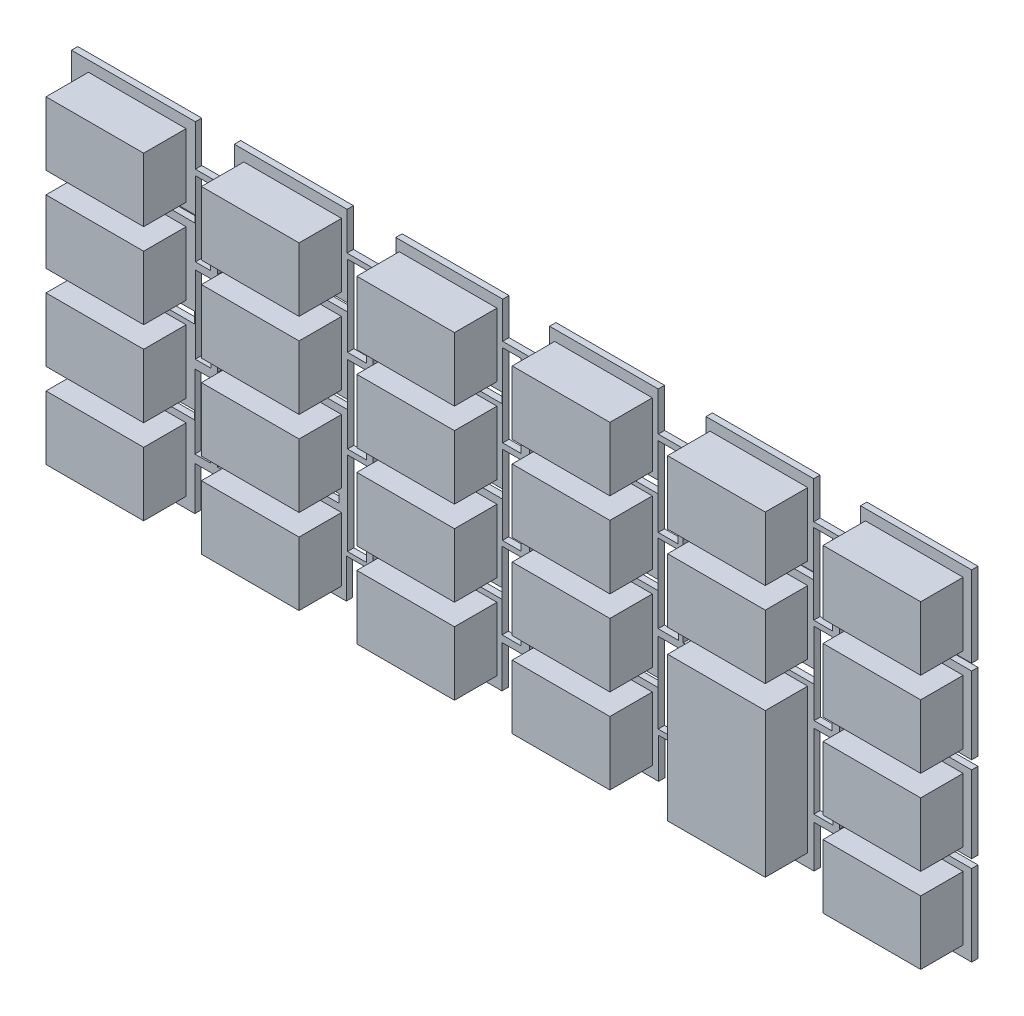
SolidWorks part; units mm, degrees
ref_plane "Front Plane" through (0, 0, 0) normal (0, 0, 1) x (1, 0, 0)
ref_plane "Top Plane" through (0, 0, 0) normal (0, 1, 0) x (1, 0, 0)
ref_plane "Right Plane" through (0, 0, 0) normal (1, 0, 0) x (0, 0, -1)
sketch "Sketch1" plane through (0, 0, 0) normal (0, 0, 1) x (1, 0, 0)
  line L1 (64.5, -22) -> (-64.5, -22)
  line L2 (64.5, -22) -> (64.5, 22)
  line L3 (64.5, 22) -> (-64.5, 22)
  line L4 (-64.5, -22) -> (-64.5, 22)
  line L5 (64.5, -22) -> (-64.5, 22) construction
  line L6 (64.5, 22) -> (-64.5, -22) construction
  point P0 (0, 0)
  dimension "D1" = 129
  dimension "D2" = 44
extrude "main_body" add sketch "Sketch1" along normal blind 0.75
sketch "Sketch2" plane through (0, 0, 0.75) normal (0, 0, 1) x (1, 0, 0)
  line L0 (46.25, 22) -> (46.25, -22) construction
  line L1 (64.5, 22) -> (-64.5, 22) construction
  line L2 (-64.5, -22) -> (64.5, -22) construction
  line L3 (64.5, -22) -> (64.5, 22) construction
  line L4 (36.95, -5) -> (36.95, -15) construction
  line L5 (27.95, -22) -> (27.95, 22) construction
  line L6 (-64.5, 22) -> (-64.5, -22) construction
  line L7 (-39.5, 11.25) -> (-51, 11.25)
  line L8 (9.65, 22) -> (9.65, -22) construction
  line L9 (-39.5, 1.25) -> (-51, 1.25)
  line L10 (64.5, 5) -> (-64.5, 5) construction
  line L11 (-8.65, -22) -> (-8.65, 22) construction
  line L12 (-39.5, 1.25) -> (-39.5, 8.75)
  line L13 (-39.5, 8.75) -> (-51, 8.75)
  line L14 (-26.95, 22) -> (-26.95, -22) construction
  line L15 (-64.5, 15) -> (64.5, 15) construction
  line L16 (-51, 1.25) -> (-51, 8.75)
  line L17 (-45.25, -22) -> (-45.25, 22) construction
  line L18 (-39.5, 1.25) -> (-51, 8.75) construction
  line L19 (64.5, -5) -> (-64.5, -5) construction
  line L20 (-39.5, 8.75) -> (-51, 1.25) construction
  line L21 (-21.2, 1.25) -> (-32.7, 1.25)
  line L22 (-64.5, -15) -> (64.5, -15) construction
  line L23 (-21.2, 1.25) -> (-21.2, 8.75)
  line L24 (-21.2, 8.75) -> (-32.7, 8.75)
  line L25 (-32.7, 1.25) -> (-32.7, 8.75)
  line L26 (-21.2, 1.25) -> (-32.7, 8.75) construction
  line L27 (-21.2, 8.75) -> (-32.7, 1.25) construction
  line L28 (-2.9, 1.25) -> (-14.4, 1.25)
  line L29 (-2.9, 1.25) -> (-2.9, 8.75)
  line L30 (-2.9, 8.75) -> (-14.4, 8.75)
  line L31 (-14.4, 1.25) -> (-14.4, 8.75)
  line L32 (-2.9, 1.25) -> (-14.4, 8.75) construction
  line L33 (-2.9, 8.75) -> (-14.4, 1.25) construction
  line L34 (15.4, 1.25) -> (3.9, 1.25)
  line L35 (15.4, 1.25) -> (15.4, 8.75)
  line L36 (15.4, 8.75) -> (3.9, 8.75)
  line L37 (3.9, 1.25) -> (3.9, 8.75)
  line L38 (15.4, 1.25) -> (3.9, 8.75) construction
  line L39 (15.4, 8.75) -> (3.9, 1.25) construction
  line L40 (33.7, 1.25) -> (22.2, 1.25)
  line L41 (33.7, 1.25) -> (33.7, 8.75)
  line L42 (33.7, 8.75) -> (22.2, 8.75)
  line L43 (22.2, 1.25) -> (22.2, 8.75)
  line L44 (33.7, 1.25) -> (22.2, 8.75) construction
  line L45 (33.7, 8.75) -> (22.2, 1.25) construction
  line L46 (52, -8.75) -> (40.5, -8.75)
  line L47 (52, -8.75) -> (52, -1.25)
  line L48 (52, -1.25) -> (40.5, -1.25)
  line L49 (40.5, -8.75) -> (40.5, -1.25)
  line L50 (52, -8.75) -> (40.5, -1.25) construction
  line L51 (52, -1.25) -> (40.5, -8.75) construction
  line L52 (52, -18.75) -> (40.5, -18.75)
  line L53 (52, -18.75) -> (52, -11.25)
  line L54 (52, -11.25) -> (40.5, -11.25)
  line L55 (40.5, -18.75) -> (40.5, -11.25)
  line L56 (52, -18.75) -> (40.5, -11.25) construction
  line L57 (52, -11.25) -> (40.5, -18.75) construction
  line L58 (52, 11.25) -> (40.5, 11.25)
  line L59 (52, 11.25) -> (52, 18.75)
  line L60 (52, 18.75) -> (40.5, 18.75)
  line L61 (40.5, 11.25) -> (40.5, 18.75)
  line L62 (52, 11.25) -> (40.5, 18.75) construction
  line L63 (52, 18.75) -> (40.5, 11.25) construction
  line L64 (-39.5, 11.25) -> (-39.5, 18.75)
  line L65 (-39.5, 18.75) -> (-51, 18.75)
  line L66 (-51, 11.25) -> (-51, 18.75)
  line L67 (-39.5, 11.25) -> (-51, 18.75) construction
  line L68 (-39.5, 18.75) -> (-51, 11.25) construction
  line L69 (-39.5, -8.75) -> (-51, -8.75)
  line L70 (-39.5, -8.75) -> (-39.5, -1.25)
  line L71 (-39.5, -1.25) -> (-51, -1.25)
  line L72 (-51, -8.75) -> (-51, -1.25)
  line L73 (-39.5, -8.75) -> (-51, -1.25) construction
  line L74 (-39.5, -1.25) -> (-51, -8.75) construction
  line L75 (-39.5, -18.75) -> (-51, -18.75)
  line L76 (-39.5, -18.75) -> (-39.5, -11.25)
  line L77 (-39.5, -11.25) -> (-51, -11.25)
  line L78 (-51, -18.75) -> (-51, -11.25)
  line L79 (-39.5, -18.75) -> (-51, -11.25) construction
  line L80 (-39.5, -11.25) -> (-51, -18.75) construction
  line L81 (-21.2, 11.25) -> (-32.7, 11.25)
  line L82 (-21.2, 11.25) -> (-21.2, 18.75)
  line L83 (-21.2, 18.75) -> (-32.7, 18.75)
  line L84 (-32.7, 11.25) -> (-32.7, 18.75)
  line L85 (-21.2, 11.25) -> (-32.7, 18.75) construction
  line L86 (-21.2, 18.75) -> (-32.7, 11.25) construction
  line L87 (-21.2, -8.75) -> (-32.7, -8.75)
  line L88 (-21.2, -8.75) -> (-21.2, -1.25)
  line L89 (-21.2, -1.25) -> (-32.7, -1.25)
  line L90 (-32.7, -8.75) -> (-32.7, -1.25)
  line L91 (-21.2, -8.75) -> (-32.7, -1.25) construction
  line L92 (-21.2, -1.25) -> (-32.7, -8.75) construction
  line L93 (-21.2, -18.75) -> (-32.7, -18.75)
  line L94 (-21.2, -18.75) -> (-21.2, -11.25)
  line L95 (-21.2, -11.25) -> (-32.7, -11.25)
  line L96 (-32.7, -18.75) -> (-32.7, -11.25)
  line L97 (-21.2, -18.75) -> (-32.7, -11.25) construction
  line L98 (-21.2, -11.25) -> (-32.7, -18.75) construction
  line L99 (-2.9, -8.75) -> (-14.4, -8.75)
  line L100 (-2.9, -8.75) -> (-2.9, -1.25)
  line L101 (-2.9, -1.25) -> (-14.4, -1.25)
  line L102 (-14.4, -8.75) -> (-14.4, -1.25)
  line L103 (-2.9, -8.75) -> (-14.4, -1.25) construction
  line L104 (-2.9, -1.25) -> (-14.4, -8.75) construction
  line L105 (-2.9, -18.75) -> (-14.4, -18.75)
  line L106 (-2.9, -18.75) -> (-2.9, -11.25)
  line L107 (-2.9, -11.25) -> (-14.4, -11.25)
  line L108 (-14.4, -18.75) -> (-14.4, -11.25)
  line L109 (-2.9, -18.75) -> (-14.4, -11.25) construction
  line L110 (-2.9, -11.25) -> (-14.4, -18.75) construction
  line L111 (-2.9, 11.25) -> (-14.4, 11.25)
  line L112 (-2.9, 11.25) -> (-2.9, 18.75)
  line L113 (-2.9, 18.75) -> (-14.4, 18.75)
  line L114 (-14.4, 11.25) -> (-14.4, 18.75)
  line L115 (-2.9, 11.25) -> (-14.4, 18.75) construction
  line L116 (-2.9, 18.75) -> (-14.4, 11.25) construction
  line L117 (15.4, 11.25) -> (3.9, 11.25)
  line L118 (15.4, 11.25) -> (15.4, 18.75)
  line L119 (15.4, 18.75) -> (3.9, 18.75)
  line L120 (3.9, 11.25) -> (3.9, 18.75)
  line L121 (15.4, 11.25) -> (3.9, 18.75) construction
  line L122 (15.4, 18.75) -> (3.9, 11.25) construction
  line L123 (15.4, -8.75) -> (3.9, -8.75)
  line L124 (15.4, -8.75) -> (15.4, -1.25)
  line L125 (15.4, -1.25) -> (3.9, -1.25)
  line L126 (3.9, -8.75) -> (3.9, -1.25)
  line L127 (15.4, -8.75) -> (3.9, -1.25) construction
  line L128 (15.4, -1.25) -> (3.9, -8.75) construction
  line L129 (15.4, -18.75) -> (3.9, -18.75)
  line L130 (15.4, -18.75) -> (15.4, -11.25)
  line L131 (15.4, -11.25) -> (3.9, -11.25)
  line L132 (3.9, -18.75) -> (3.9, -11.25)
  line L133 (15.4, -18.75) -> (3.9, -11.25) construction
  line L134 (15.4, -11.25) -> (3.9, -18.75) construction
  line L135 (33.7, 11.25) -> (22.2, 11.25)
  line L136 (33.7, 11.25) -> (33.7, 18.75)
  line L137 (33.7, 18.75) -> (22.2, 18.75)
  line L138 (22.2, 11.25) -> (22.2, 18.75)
  line L139 (33.7, 11.25) -> (22.2, 18.75) construction
  line L140 (33.7, 18.75) -> (22.2, 11.25) construction
  line L141 (52, 1.25) -> (40.5, 1.25)
  line L142 (52, 1.25) -> (52, 8.75)
  line L143 (52, 8.75) -> (40.5, 8.75)
  line L144 (40.5, 1.25) -> (40.5, 8.75)
  line L145 (52, 1.25) -> (40.5, 8.75) construction
  line L146 (52, 8.75) -> (40.5, 1.25) construction
  line L147 (36.95, -10) -> (27.95, -10) construction
  line L149 (33.7, -18.5) -> (22.2, -18.5)
  line L150 (33.7, -18.5) -> (33.7, -1.5)
  line L151 (33.7, -1.5) -> (22.2, -1.5)
  line L152 (22.2, -18.5) -> (22.2, -1.5)
  line L153 (33.7, -18.5) -> (22.2, -1.5) construction
  line L154 (33.7, -1.5) -> (22.2, -18.5) construction
  point P13 (-45.25, 15)
  point P23 (-45.25, 5)
  point P35 (-26.95, 5)
  point P40 (-8.65, 5)
  point P45 (9.65, 5)
  point P50 (27.95, 5)
  point P55 (46.25, -5)
  point P60 (46.25, -15)
  point P65 (46.25, 15)
  point P70 (-45.25, -5)
  point P75 (-45.25, -15)
  point P80 (-26.95, 15)
  point P88 (-26.95, -5)
  point P93 (-26.95, -15)
  point P98 (-8.65, -15)
  point P100 (-8.65, -5)
  point P108 (-8.65, 15)
  point P113 (9.65, 15)
  point P118 (9.65, -5)
  point P123 (9.65, -15)
  point P128 (27.95, 15)
  point P133 (46.25, 5)
  point P142 (27.95, -10)
  dimension "D1" = 18.25
  dimension "D3" = 18.3
  dimension "D4" = 18.3
  dimension "D5" = 18.3
  dimension "D6" = 18.3
  dimension "D7" = 10
  dimension "D8" = 7
  dimension "D9" = 10
  dimension "D10" = 10
  dimension "D11" = 11.5
  dimension "D12" = 11.5
  dimension "D13" = 11.5
  dimension "D14" = 11.5
  dimension "D15" = 7.5
  dimension "D16" = 7.5
  dimension "D17" = 7.5
  dimension "D18" = 7.5
  dimension "D19" = 7.5
  dimension "D20" = 7.5
  dimension "D21" = 11.5
  dimension "D22" = 11.5
  dimension "D23" = 7.5
  dimension "D24" = 11.5
  dimension "D25" = 11.5
  dimension "D26" = 7.5
  dimension "D27" = 7
  dimension "D28" = 18.3
  dimension "D29" = 19.25
  dimension "D30" = 9
  dimension "D31" = 5
  dimension "D32" = 5
  dimension "D33" = 11.5
  dimension "D34" = 7.5
  dimension "D35" = 11.5
  dimension "D36" = 7.5
  dimension "D37" = 11.5
  dimension "D38" = 7.5
  dimension "D39" = 11.5
  dimension "D40" = 7.5
  dimension "D41" = 11.5
  dimension "D42" = 7.5
  dimension "D43" = 11.5
  dimension "D44" = 7.5
  dimension "D45" = 11.5
  dimension "D46" = 17
  dimension "D47" = 11.5
  dimension "D48" = 7.5
  dimension "D49" = 11.5
  dimension "D50" = 7.5
  dimension "D51" = 11.5
  dimension "D52" = 11.5
  dimension "D53" = 11.5
  dimension "D54" = 11.5
  dimension "D55" = 11.5
  dimension "D56" = 11.5
  dimension "D57" = 7.5
  dimension "D58" = 7.5
  dimension "D59" = 7.5
  dimension "D60" = 7.5
  dimension "D61" = 7.5
  dimension "D62" = 7.5
extrude "button_bumps" add sketch "Sketch2" along normal blind 5
fillet "button_corners" [suppressed] radius 1
fillet "button_top" [suppressed] radius 1
sketch "Sketch3" [suppressed] plane through (0, 0, 5.5) normal (0, 0, 1) x (1, 0, 0)
  line L0 (-50.5, 22) -> (-50.5, -22) construction
  line L1 (61.5, 22) -> (-61.5, 22) construction
  line L2 (-61.5, -22) -> (61.5, -22) construction
  line L3 (-32.2, 22) -> (-32.2, -22) construction
  line L4 (64.5, -19) -> (64.5, 19) construction
  line L5 (-52.25, 14.5) -> (-38.25, 14.5) construction
  line L6 (-52.25, 18) -> (-52.25, 12) construction
  line L7 (-13.9, 22) -> (-13.9, -22) construction
  line L8 (-38.25, 12) -> (-38.25, 18) construction
  line L9 (2.65, -12) -> (2.65, -18) construction
  line L10 (20.95, -2.5) -> (20.95, -17.5) construction
  line L11 (39.25, -12) -> (39.25, -18) construction
  line L12 (-15.65, -12) -> (-15.65, -18) construction
  line L13 (4.4, -22) -> (4.4, 22) construction
  line L14 (-33.95, -12) -> (-33.95, -18) construction
  line L15 (-52.25, -12) -> (-52.25, -18) construction
  line L16 (22.7, 22) -> (22.7, -22) construction
  line L17 (-64.5, 13.5) -> (64.5, 13.5) construction
  line L18 (-64.5, 19) -> (-64.5, -19) construction
  line L19 (41, -22) -> (41, 22) construction
  line L20 (-64.5, 3.5) -> (64.5, 3.5) construction
  line L21 (-52.25, 4.5) -> (-38.25, 4.5) construction
  line L22 (-52.25, 8) -> (-52.25, 2) construction
  line L23 (-64.5, -6.5) -> (64.5, -6.5) construction
  line L24 (-38.25, 2) -> (-38.25, 8) construction
  line L25 (-52.25, -15.5) -> (-38.25, -15.5) construction
  line L26 (64.5, -16.5) -> (-64.5, -16.5) construction
  line L27 (-52.25, -12) -> (-52.25, -18) construction
  line L28 (-38.25, -8) -> (-38.25, -2) construction
  line L29 (-38.25, -5.5) -> (-52.25, -5.5) construction
  line L30 (-52.25, -2) -> (-52.25, -8) construction
  line L31 (-38.25, -18) -> (-38.25, -12) construction
  line L32 (-33.95, 12.5) -> (34.95, 12.5) construction
  line L33 (-33.95, 18) -> (-33.95, 12) construction
  line L34 (34.95, 12) -> (34.95, 18) construction
  line L35 (-33.95, 2.5) -> (34.95, 2.5) construction
  line L36 (-21.35, 19) -> (-21.35, -19) construction
  line L37 (-20.95, 19) -> (-32.95, 19) construction
  line L38 (-33.95, 8) -> (-33.95, 2) construction
  line L39 (34.95, 2) -> (34.95, 8) construction
  line L40 (-32.95, -19) -> (-20.95, -19) construction
  line L41 (-33.95, -7.5) -> (34.95, -7.5) construction
  line L42 (-19.95, -18) -> (-19.95, -12) construction
  line L43 (-33.95, -2) -> (-33.95, -8) construction
  line L44 (34.95, -17.5) -> (34.95, -2.5) construction
  line L45 (-3.05, 19) -> (-3.05, -19) construction
  line L46 (-33.95, -17.5) -> (34.95, -17.5) construction
  line L47 (-2.65, 19) -> (-14.65, 19) construction
  line L48 (-14.65, -19) -> (-2.65, -19) construction
  line L49 (-33.95, -12) -> (-33.95, -18) construction
  line L50 (-33.95, 15.3) -> (34.95, 15.3) construction
  line L51 (-33.95, 5.3) -> (34.95, 5.3) construction
  line L52 (-33.95, -4.7) -> (34.95, -4.7) construction
  line L53 (-33.95, -14.7) -> (34.95, -14.7) construction
  line L54 (-1.65, -18) -> (-1.65, -12) construction
  line L55 (-4.6, -14.55) -> (-3.2, -14.55)
  line L56 (15.25, 19) -> (15.25, -19) construction
  line L57 (-3.05, -14.7) -> (-4.75, -14.7)
  line L58 (15.65, 19) -> (3.65, 19) construction
  line L59 (-3.05, -14.7) -> (-3.05, -14.55)
  line L60 (3.65, -19) -> (15.65, -19) construction
  line L62 (33.55, 19) -> (33.55, -18.5) construction
  line L63 (33.95, 19) -> (21.95, 19) construction
  line L64 (21.95, -18.5) -> (33.95, -18.5) construction
  line L65 (16.65, -18) -> (16.65, -12) construction
  line L66 (34.95, -17.5) -> (34.95, -2.5) construction
  line L67 (-4.75, -14.7) -> (-4.75, -14.55)
  line L69 (-4.75, -14.55) -> (-4.75, -14.4)
  line L70 (-4.75, -14.4) -> (-4.6, -14.4)
  line L71 (-4.6, -14.55) -> (-4.6, -14.4)
  line L73 (-3.05, -14.55) -> (-3.05, -14.4)
  line L74 (-3.05, -14.4) -> (-3.2, -14.4)
  line L75 (-3.2, -14.55) -> (-3.2, -14.4)
  line L76 (39.25, 13.8) -> (53.25, 13.8) construction
  line L77 (39.25, 18) -> (39.25, 12) construction
  line L78 (53.25, 12) -> (53.25, 18) construction
  line L79 (39.25, 3.8) -> (53.25, 3.8) construction
  line L80 (39.25, 8) -> (39.25, 2) construction
  line L81 (53.25, 2) -> (53.25, 8) construction
  line L82 (39.25, -6.2) -> (53.25, -6.2) construction
  line L83 (39.25, -2) -> (39.25, -8) construction
  line L84 (53.25, -8) -> (53.25, -2) construction
  line L85 (39.25, -16.2) -> (53.25, -16.2) construction
  line L86 (39.25, -12) -> (39.25, -18) construction
  line L87 (53.25, -18) -> (53.25, -12) construction
  line L88 (-52.25, 12.5) -> (-38.25, 12.5) construction
  line L89 (-52.25, 18) -> (-52.25, 12) construction
  line L90 (-38.25, 12) -> (-38.25, 18) construction
  line L91 (-52.25, 2.5) -> (-38.25, 2.5) construction
  line L92 (-52.25, -7.5) -> (-38.25, -7.5) construction
  line L93 (-52.25, -17.5) -> (-38.25, -17.5) construction
  text T0 "1" font "Arial Narrow" height in points 14
  text T1 "SSB" font "Arial Narrow" height in points 10
  text T2 "4" font "Arial Narrow" height in points 14
  text T3 "2" font "Arial Narrow" height in points 14
  text T4 "3" font "Arial Narrow" height in points 14
  text T5 "5" font "Arial Narrow" height in points 14
  text T6 "6" font "Arial Narrow" height in points 14
  text T7 "7" font "Arial Narrow" height in points 14
  text T8 "8" font "Arial Narrow" height in points 14
  text T9 "9" font "Arial Narrow" height in points 14
  text T10 "." font "Arial Rounded MT Bold" height in points 14
  text T11 "0" font "Arial Narrow" height in points 14
  text T12 "C" font "Arial Narrow" height in points 14
  text T13 "M" font "Arial Narrow" height in points 14
  text T14 "S" font "Arial Narrow" height in points 14
  text T15 "CW" font "Arial Narrow" height in points 10
  text T16 "AM" font "Arial Narrow" height in points 10
  text T17 "FIX" font "Arial Narrow" height in points 10
  text T18 "             160m" font "Arial Narrow" height in points 6
  text T19 "               30m" font "Arial Narrow" height in points 6
  text T20 "               12m" font "Arial Narrow" height in points 6
  text T21 "                 4m" font "Arial Narrow" height in points 6
  text T22 "               80m" font "Arial Narrow" height in points 6
  text T23 "               20m" font "Arial Narrow" height in points 6
  text T24 "               10m" font "Arial Narrow" height in points 6
  text T25 "                  LF" font "Arial Narrow" height in points 6
  text T26 "               60m" font "Arial Narrow" height in points 6
  text T27 "               17m" font "Arial Narrow" height in points 6
  text T28 "                 6m" font "Arial Narrow" height in points 6
  text T29 "                 MF" font "Arial Narrow" height in points 6
  text T30 "               40m" font "Arial Narrow" height in points 6
  text T31 "               15m" font "Arial Narrow" height in points 6
  text T32 "          ENTER" font "Arial Narrow" height in points 6
  text T33 "           ABC" font "Arial Narrow" height in points 7
  text T34 "           DEF" font "Arial Narrow" height in points 7
  text T35 "            GHI" font "Arial Narrow" height in points 7
  text T36 "             JKL" font "Arial Narrow" height in points 7
  text T37 "          MNO" font "Arial Narrow" height in points 7
  text T38 "         PQRS" font "Arial Narrow" height in points 7
  text T39 "           TUV" font "Arial Narrow" height in points 7
  text T40 "        WXYZ" font "Arial Narrow" height in points 7
  text T41 "              */--" font "Arial Narrow" height in points 7
  text T42 "         ↵" font "Lucida Sans Unicode" height in points 7
  text T43 "   DSP" font "Arial Narrow" height in points 10
  text T44 "  STEP" font "Arial Narrow" height in points 10
  text T45 "FILTER" font "Arial Narrow" height in points 10
  text T46 "  SPLIT" font "Arial Narrow" height in points 10
  text T47 "                   LSB/USB" font "Arial Narrow" height in points 4
  text T48 "                      KEYER" font "Arial Narrow" height in points 4
  text T49 "                    FM/DIGI" font "Arial Narrow" height in points 4
  text T50 "                   CENTER" font "Arial Narrow" height in points 4
  dimension "D1" = 23.5
  dimension "D2" = 18.3
  dimension "D3" = 18.3
  dimension "D4" = 18.3
  dimension "D5" = 18.3
  dimension "D6" = 18.3
  dimension "D7" = 1.75
  dimension "D8" = 1.75
  dimension "D9" = 1.75
  dimension "D10" = 1.75
  dimension "D11" = 1.75
  dimension "D12" = 1.75
  dimension "D13" = 10
  dimension "D14" = 10
  dimension "D15" = 10
  dimension "D16" = 8.5
  dimension "D17" = 5.5
  dimension "D18" = 1
  dimension "D19" = 1
  dimension "D20" = 1
  dimension "D21" = 1
  dimension "D22" = 1
  dimension "D23" = 1
  dimension "D24" = 1
  dimension "D25" = 1
  dimension "D26" = 1.8
  dimension "D27" = 1.8
  dimension "D28" = 1.8
  dimension "D29" = 1.8
  dimension "D30" = 1.4
  dimension "D31" = 1.4
  dimension "D32" = 1.4
  dimension "D33" = 1.4
  dimension "D34" = 1.7
  dimension "D35" = 0.15
  dimension "D36" = 0.3
  dimension "D37" = 0.15
  dimension "D38" = 0.15
  dimension "D39" = 0.15
  dimension "D40" = 0.15
  dimension "D41" = 0.15
  dimension "D42" = 0.15
  dimension "D43" = 0.3
  dimension "D44" = 0.3
  dimension "D45" = 0.3
  dimension "D46" = 1
  dimension "D47" = 1
  dimension "D48" = 1
  dimension "D49" = 1
extrude "buttons_text" [suppressed] add sketch "Sketch3" along normal blind 0.1
sketch "Sketch5" plane through (0, 0, 0.75) normal (0, 0, 1) x (1, 0, 0)
  line L62 (-53, 20) -> (53, 20)
  line L63 (-53, 20) -> (-53, -20)
  line L64 (-53, -20) -> (53, -20)
  line L65 (53, 20) -> (53, -20)
  dimension "D1" = 106
  dimension "D2" = 40
  dimension "D3" = 20
  dimension "D4" = 53
extrude "corners_cut" cut sketch "Sketch5" against normal through all flip side to cut
sketch "Sketch6" plane through (0, 0, 0.75) normal (0, 0, 1) x (1, 0, 0)
  line L0 (-53, 20) -> (-53, -20) construction
  line L1 (-53, 10.487) -> (-38.4318, 10.487)
  line L2 (-53, 10.487) -> (-53, 9.639)
  line L3 (-53, 9.639) -> (-38.4318, 9.639)
  line L4 (-38.4318, 10.487) -> (-38.4318, 9.639)
  line L5 (53, 20) -> (-53, 20) construction
  line L6 (-53, 0.6278) -> (-38.5268, 0.6278)
  line L7 (-53, 0.6278) -> (-53, -0.6772)
  line L8 (-53, -0.6772) -> (-38.5268, -0.6772)
  line L9 (-38.5268, 0.6278) -> (-38.5268, -0.6772)
  line L10 (-53, -9.4645) -> (-38.4947, -9.4645)
  line L11 (-53, -9.4645) -> (-53, -10.4595)
  line L12 (-53, -10.4595) -> (-38.4947, -10.4595)
  line L13 (-38.4947, -9.4645) -> (-38.4947, -10.4595)
  line L14 (-38.4124, 20) -> (-33.8283, 20)
  line L15 (-38.4124, 20) -> (-38.4124, 15.1621)
  line L16 (-38.4124, 15.1621) -> (-33.8283, 15.1621)
  line L17 (-33.8283, 20) -> (-33.8283, 15.1621)
  line L18 (-53, -20) -> (53, -20) construction
  line L23 (53, -20) -> (53, 20) construction
  line L24 (-20.5465, 20) -> (-14.8109, 20)
  line L25 (-20.5465, 20) -> (-20.5465, 15.5362)
  line L26 (-20.5465, 15.5362) -> (-14.8109, 15.5362)
  line L27 (-14.8109, 20) -> (-14.8109, 15.5362)
  line L28 (-2.2207, 20) -> (3.2938, 20)
  line L29 (-2.2207, 20) -> (-2.2207, 15.7023)
  line L30 (-2.2207, 15.7023) -> (3.2938, 15.7023)
  line L31 (3.2938, 20) -> (3.2938, 15.7023)
  line L32 (16.0959, 20) -> (21.7218, 20)
  line L33 (16.0959, 20) -> (16.0959, 15.3985)
  line L34 (16.0959, 15.3985) -> (21.7218, 15.3985)
  line L35 (21.7218, 20) -> (21.7218, 15.3985)
  line L36 (34.4017, 20) -> (39.911, 20)
  line L37 (34.4017, 20) -> (34.4017, 15.6134)
  line L38 (34.4017, 15.6134) -> (39.911, 15.6134)
  line L39 (39.911, 20) -> (39.911, 15.6134)
  line L40 (-20.6305, -20) -> (-15.0655, -20)
  line L41 (-20.6305, -20) -> (-20.6305, -15.3916)
  line L42 (-20.6305, -15.3916) -> (-15.0655, -15.3916)
  line L43 (-15.0655, -20) -> (-15.0655, -15.3916)
  line L44 (-2.3118, -20) -> (3.1497, -20)
  line L45 (-2.3118, -20) -> (-2.3118, -15.0585)
  line L46 (-2.3118, -15.0585) -> (3.1497, -15.0585)
  line L47 (3.1497, -20) -> (3.1497, -15.0585)
  line L48 (16.1416, -20) -> (21.3808, -20)
  line L49 (16.1416, -20) -> (16.1416, -15.2957)
  line L50 (16.1416, -15.2957) -> (21.3808, -15.2957)
  line L51 (21.3808, -20) -> (21.3808, -15.2957)
  line L52 (34.4363, -20) -> (39.9725, -20)
  line L53 (34.4363, -20) -> (34.4363, -15.0209)
  line L54 (34.4363, -15.0209) -> (39.9725, -15.0209)
  line L55 (39.9725, -20) -> (39.9725, -15.0209)
  line L61 (53, 0.6278) -> (40.0214, 0.6278)
  line L62 (53, 0.6278) -> (53, -0.4027)
  line L63 (53, -0.4027) -> (40.0214, -0.4027)
  line L64 (40.0214, 0.6278) -> (40.0214, -0.4027)
  line L65 (53, 10.487) -> (39.968, 10.487)
  line L66 (53, 10.487) -> (53, 9.6837)
  line L67 (53, 9.6837) -> (39.968, 9.6837)
  line L68 (39.968, 10.487) -> (39.968, 9.6837)
  line L73 (-38.4124, 14.5006) -> (-36.6167, 14.5006)
  line L74 (-38.4124, 14.5006) -> (-38.4124, 5.7068)
  line L75 (-38.4124, 5.7068) -> (-36.6167, 5.7068)
  line L76 (-36.6167, 14.5006) -> (-36.6167, 5.7068)
  line L81 (-38.4755, -13.9249) -> (-36.6481, -13.9249)
  line L82 (-38.4755, -13.9249) -> (-38.4755, -5.2376)
  line L83 (-38.4755, -5.2376) -> (-36.6481, -5.2376)
  line L84 (-36.6481, -13.9249) -> (-36.6481, -5.2376)
  line L97 (-38.4237, 4.89) -> (-36.5843, 4.89)
  line L98 (-38.4237, 4.89) -> (-38.4237, -4.2234)
  line L99 (-38.4237, -4.2234) -> (-36.5843, -4.2234)
  line L100 (-36.5843, 4.89) -> (-36.5843, -4.2234)
  line L101 (-35.7933, 4.8665) -> (-33.5064, 4.8665)
  line L102 (-35.7933, 4.8665) -> (-35.7933, -4.2413)
  line L103 (-35.7933, -4.2413) -> (-33.5064, -4.2413)
  line L104 (-33.5064, 4.8665) -> (-33.5064, -4.2413)
  line L105 (-33.819, 10.487) -> (-20.5046, 10.487)
  line L106 (-33.819, 10.487) -> (-33.819, 9.5573)
  line L107 (-33.819, 9.5573) -> (-20.5046, 9.5573)
  line L108 (-20.5046, 10.487) -> (-20.5046, 9.5573)
  line L109 (-33.4426, 0.6278) -> (-20.5096, 0.6278)
  line L110 (-33.4426, 0.6278) -> (-33.4426, -0.4027)
  line L111 (-33.4426, -0.4027) -> (-20.5096, -0.4027)
  line L112 (-20.5096, 0.6278) -> (-20.5096, -0.4027)
  line L113 (-33.5346, -9.4645) -> (-21.4766, -9.4645)
  line L114 (-33.5346, -9.4645) -> (-33.5346, -10.4595)
  line L115 (-33.5346, -10.4595) -> (-21.4766, -10.4595)
  line L116 (-21.4766, -9.4645) -> (-21.4766, -10.4595)
  line L117 (-14.7699, 10.487) -> (-2.2829, 10.487)
  line L118 (-14.7699, 10.487) -> (-14.7699, 9.3006)
  line L119 (-14.7699, 9.3006) -> (-2.2829, 9.3006)
  line L120 (-2.2829, 10.487) -> (-2.2829, 9.3006)
  line L121 (-14.8344, 0.6278) -> (-2.2687, 0.6278)
  line L122 (-14.8344, 0.6278) -> (-14.8344, -0.4027)
  line L123 (-14.8344, -0.4027) -> (-2.2687, -0.4027)
  line L124 (-2.2687, 0.6278) -> (-2.2687, -0.4027)
  line L125 (-14.8364, -9.4645) -> (-2.3087, -9.4645)
  line L126 (-14.8364, -9.4645) -> (-14.8364, -10.6477)
  line L127 (-14.8364, -10.6477) -> (-2.3087, -10.6477)
  line L128 (-2.3087, -9.4645) -> (-2.3087, -10.6477)
  line L141 (21.7364, 10.487) -> (34.3679, 10.487)
  line L142 (21.7364, 10.487) -> (21.7364, 9.6837)
  line L143 (21.7364, 9.6837) -> (34.3679, 9.6837)
  line L144 (34.3679, 10.487) -> (34.3679, 9.6837)
  line L149 (53.0113, -9.4645) -> (40.0275, -9.4645)
  line L150 (53.0113, -9.4645) -> (53.0113, -10.4595)
  line L151 (53.0113, -10.4595) -> (40.0275, -10.4595)
  line L152 (40.0275, -9.4645) -> (40.0275, -10.4595)
  line L153 (37.4431, 4.8871) -> (40.011, 4.8871)
  line L154 (37.4431, 4.8871) -> (37.4431, -4.6496)
  line L155 (37.4431, -4.6496) -> (40.011, -4.6496)
  line L156 (40.011, 4.8871) -> (40.011, -4.6496)
  line L157 (37.4599, 15.0198) -> (39.9551, 15.0198)
  line L158 (37.4599, 15.0198) -> (37.4599, 5.552)
  line L159 (37.4599, 5.552) -> (39.9551, 5.552)
  line L160 (39.9551, 15.0198) -> (39.9551, 5.552)
  line L161 (19.0294, 14.7329) -> (21.7058, 14.7329)
  line L162 (19.0294, 14.7329) -> (19.0294, 5.3578)
  line L163 (19.0294, 5.3578) -> (21.7058, 5.3578)
  line L164 (21.7058, 14.7329) -> (21.7058, 5.3578)
  line L165 (16.0811, 4.7899) -> (18.4829, 4.7899)
  line L166 (16.0811, 4.7899) -> (16.0811, -4.4502)
  line L167 (16.0811, -4.4502) -> (18.4829, -4.4502)
  line L168 (18.4829, 4.7899) -> (18.4829, -4.4502)
  line L169 (-2.2558, 4.6853) -> (-0.0559, 4.6853)
  line L170 (-2.2558, 4.6853) -> (-2.2558, -4.6264)
  line L171 (-2.2558, -4.6264) -> (-0.0559, -4.6264)
  line L172 (-0.0559, 4.6853) -> (-0.0559, -4.6264)
  line L173 (0.9534, 15.067) -> (3.3538, 15.067)
  line L174 (0.9534, 15.067) -> (0.9534, 5.3765)
  line L175 (0.9534, 5.3765) -> (3.3538, 5.3765)
  line L176 (3.3538, 15.067) -> (3.3538, 5.3765)
  line L177 (-20.4967, 4.7067) -> (-18.255, 4.7067)
  line L178 (-20.4967, 4.7067) -> (-20.4967, -4.4194)
  line L179 (-20.4967, -4.4194) -> (-18.255, -4.4194)
  line L180 (-18.255, 4.7067) -> (-18.255, -4.4194)
  line L181 (-17.508, 14.9557) -> (-14.7882, 14.9557)
  line L182 (-17.508, 14.9557) -> (-17.508, 5.4415)
  line L183 (-17.508, 5.4415) -> (-14.7882, 5.4415)
  line L184 (-14.7882, 14.9557) -> (-14.7882, 5.4415)
  line L185 (34.4168, -5.4308) -> (36.6803, -5.4308)
  line L186 (34.4168, -5.4308) -> (34.4168, -14.2037)
  line L187 (34.4168, -14.2037) -> (36.6803, -14.2037)
  line L188 (36.6803, -5.4308) -> (36.6803, -14.2037)
  line L189 (34.4585, 4.972) -> (36.5623, 4.972)
  line L190 (34.4585, 4.972) -> (34.4585, -4.6433)
  line L191 (34.4585, -4.6433) -> (36.5623, -4.6433)
  line L192 (36.5623, 4.972) -> (36.5623, -4.6433)
  line L193 (34.4017, 15.0307) -> (36.5971, 15.0307)
  line L194 (34.4017, 15.0307) -> (34.4017, 5.5725)
  line L195 (34.4017, 5.5725) -> (36.5971, 5.5725)
  line L196 (36.5971, 15.0307) -> (36.5971, 5.5725)
  line L197 (16.0847, 5.3628) -> (18.452, 5.3628)
  line L198 (16.0847, 5.3628) -> (16.0847, 14.7218)
  line L199 (16.0847, 14.7218) -> (18.452, 14.7218)
  line L200 (18.452, 5.3628) -> (18.452, 14.7218)
  line L201 (-2.2207, 15.0439) -> (-0.0452, 15.0439)
  line L202 (-2.2207, 15.0439) -> (-2.2207, 5.3424)
  line L203 (-2.2207, 5.3424) -> (-0.0452, 5.3424)
  line L204 (-0.0452, 15.0439) -> (-0.0452, 5.3424)
  line L205 (-20.4922, 14.9466) -> (-18.2555, 14.9466)
  line L206 (-20.4922, 14.9466) -> (-20.4922, 5.4415)
  line L207 (-20.4922, 5.4415) -> (-18.2555, 5.4415)
  line L208 (-18.2555, 14.9466) -> (-18.2555, 5.4415)
  line L209 (-17.5036, 4.7276) -> (-14.8461, 4.7276)
  line L210 (-17.5036, 4.7276) -> (-17.5036, -4.4171)
  line L211 (-17.5036, -4.4171) -> (-14.8461, -4.4171)
  line L212 (-14.8461, 4.7276) -> (-14.8461, -4.4171)
  line L213 (-2.299, -5.2268) -> (-0.0558, -5.2268)
  line L214 (-2.299, -5.2268) -> (-2.299, -14.2741)
  line L215 (-2.299, -14.2741) -> (-0.0558, -14.2741)
  line L216 (-0.0558, -5.2268) -> (-0.0558, -14.2741)
  line L217 (19.0218, 4.7331) -> (21.7578, 4.7331)
  line L218 (19.0218, 4.7331) -> (19.0218, -4.415)
  line L219 (19.0218, -4.415) -> (21.7578, -4.415)
  line L220 (21.7578, 4.7331) -> (21.7578, -4.415)
  line L221 (-35.8236, 14.5006) -> (-33.8283, 14.5006)
  line L222 (-35.8236, 14.5006) -> (-35.8236, 5.7204)
  line L223 (-35.8236, 5.7204) -> (-33.8283, 5.7204)
  line L224 (-33.8283, 14.5006) -> (-33.8283, 5.7204)
  line L225 (-35.7933, -5.3926) -> (-33.5611, -5.3926)
  line L226 (-35.7933, -5.3926) -> (-35.7933, -13.9249)
  line L227 (-35.7933, -13.9249) -> (-33.5611, -13.9249)
  line L228 (-33.5611, -5.3926) -> (-33.5611, -13.9249)
  line L229 (-33.5503, -20.001) -> (-38.4755, -20.001)
  line L230 (-33.5503, -20.001) -> (-33.5503, -14.8705)
  line L231 (-33.5503, -14.8705) -> (-38.4755, -14.8705)
  line L232 (-38.4755, -20.001) -> (-38.4755, -14.8705)
  line L237 (-20.4967, -5.0185) -> (-18.255, -5.0185)
  line L238 (-20.4967, -5.0185) -> (-20.4967, -14.8705)
  line L239 (-20.4967, -14.8705) -> (-18.255, -14.8705)
  line L240 (-18.255, -5.0185) -> (-18.255, -14.8705)
  line L241 (-17.5036, -5.0185) -> (-14.8461, -5.0185)
  line L242 (-17.5036, -5.0185) -> (-17.5036, -14.8705)
  line L243 (-17.5036, -14.8705) -> (-14.8461, -14.8705)
  line L244 (-14.8461, -5.0185) -> (-14.8461, -14.8705)
  line L245 (0.9534, 4.3611) -> (3.3538, 4.3611)
  line L246 (0.9534, 4.3611) -> (0.9534, -4.6264)
  line L247 (0.9534, -4.6264) -> (3.3538, -4.6264)
  line L248 (3.3538, 4.3611) -> (3.3538, -4.6264)
  line L249 (0.9534, -5.2268) -> (3.2938, -5.2268)
  line L250 (0.9534, -5.2268) -> (0.9534, -14.2741)
  line L251 (0.9534, -14.2741) -> (3.2938, -14.2741)
  line L252 (3.2938, -5.2268) -> (3.2938, -14.2741)
  line L253 (3.3634, 10.6849) -> (16.0701, 10.6849)
  line L254 (3.3634, 10.6849) -> (3.3634, 9.2912)
  line L255 (3.3634, 9.2912) -> (16.0701, 9.2912)
  line L256 (16.0701, 10.6849) -> (16.0701, 9.2912)
  line L261 (3.3694, 0.5495) -> (16.0509, 0.5495)
  line L262 (3.3694, 0.5495) -> (3.3694, -0.5761)
  line L263 (3.3694, -0.5761) -> (16.0509, -0.5761)
  line L264 (16.0509, 0.5495) -> (16.0509, -0.5761)
  line L269 (3.3073, -9.4645) -> (16.0753, -9.4645)
  line L270 (3.3073, -9.4645) -> (3.3073, -10.4595)
  line L271 (3.3073, -10.4595) -> (16.0753, -10.4595)
  line L272 (16.0753, -9.4645) -> (16.0753, -10.4595)
  line L277 (16.0811, -5.2268) -> (18.4829, -5.2268)
  line L278 (16.0811, -5.2268) -> (16.0811, -14.6884)
  line L279 (16.0811, -14.6884) -> (18.4829, -14.6884)
  line L280 (18.4829, -5.2268) -> (18.4829, -14.6884)
  line L281 (19.0218, -5.2368) -> (21.7578, -5.2368)
  line L282 (19.0218, -5.2368) -> (19.0218, -14.6884)
  line L283 (19.0218, -14.6884) -> (21.7578, -14.6884)
  line L284 (21.7578, -5.2368) -> (21.7578, -14.6884)
  line L289 (21.7852, 0.6278) -> (34.4327, 0.6278)
  line L290 (21.7852, 0.6278) -> (21.7852, -0.9337)
  line L291 (21.7852, -0.9337) -> (34.4327, -0.9337)
  line L292 (34.4327, 0.6278) -> (34.4327, -0.9337)
  line L293 (37.4431, -5.5236) -> (40.011, -5.5236)
  line L294 (37.4431, -5.5236) -> (37.4431, -14.2037)
  line L295 (37.4431, -14.2037) -> (40.011, -14.2037)
  line L296 (40.011, -5.5236) -> (40.011, -14.2037)
extrude "inkeys_cut" cut sketch "Sketch6" against normal through all
sketch "Sketch7" plane through (0, 0, 5.75) normal (0, 0, 1) x (1, 0, 0)
  line L0 (52, -15) -> (-51, -15) construction
  line L1 (52, -18.75) -> (52, -11.25) construction
  line L2 (-51, -11.25) -> (-51, -18.75) construction
  line L3 (-26.95, -18.75) -> (-26.95, 18.75) construction
  line L4 (52, -8.75) -> (52, -1.25) construction
  line L5 (52, -5) -> (-51, -5) construction
  line L6 (-51, -1.25) -> (-51, -8.75) construction
  line L7 (-32.7, -18.75) -> (-21.2, -18.75) construction
  line L8 (52, 1.25) -> (52, 8.75) construction
  line L9 (52, 5) -> (-51, 5) construction
  line L10 (-51, 8.75) -> (-51, 1.25) construction
  line L11 (-21.2, 18.75) -> (-32.7, 18.75) construction
  line L12 (52, 11.25) -> (52, 18.75) construction
  line L13 (52, 15) -> (-51, 15) construction
  line L14 (-51, 18.75) -> (-51, 11.25) construction
  line L15 (27.95, -18.5) -> (27.95, 18.75) construction
  line L16 (-39.5, 18.75) -> (-51, 18.75) construction
  line L17 (-45.25, 18.75) -> (-45.25, -18.75) construction
  line L18 (-51, -18.75) -> (-39.5, -18.75) construction
  line L19 (22.2, -18.5) -> (33.7, -18.5) construction
  line L21 (33.7, 18.75) -> (22.2, 18.75) construction
  line L23 (22.2, -10) -> (33.7, -10) construction
  line L24 (-2.9, 18.75) -> (-14.4, 18.75) construction
  line L25 (-8.65, 18.75) -> (-8.65, -18.75) construction
  line L26 (-14.4, -18.75) -> (-2.9, -18.75) construction
  line L28 (15.4, 18.75) -> (3.9, 18.75) construction
  line L29 (9.65, 18.75) -> (9.65, -18.75) construction
  line L30 (3.9, -18.75) -> (15.4, -18.75) construction
  line L34 (22.2, -1.5) -> (22.2, -18.5) construction
  line L35 (52, 18.75) -> (40.5, 18.75) construction
  line L36 (46.25, 18.75) -> (46.25, -18.75) construction
  line L37 (40.5, -18.75) -> (52, -18.75) construction
  line L38 (33.7, -18.5) -> (33.7, -1.5) construction
  line L39 (-41.875, 11.625) -> (-48.625, 11.625)
  line L40 (-41.875, 11.625) -> (-41.875, 18.375)
  line L41 (-41.875, 18.375) -> (-48.625, 18.375)
  line L42 (-48.625, 11.625) -> (-48.625, 18.375)
  line L43 (-41.875, 11.625) -> (-48.625, 18.375) construction
  line L44 (-41.875, 18.375) -> (-48.625, 11.625) construction
  line L45 (-41.875, 1.625) -> (-48.625, 1.625)
  line L46 (-41.875, 1.625) -> (-41.875, 8.375)
  line L47 (-41.875, 8.375) -> (-48.625, 8.375)
  line L48 (-48.625, 1.625) -> (-48.625, 8.375)
  line L49 (-41.875, 1.625) -> (-48.625, 8.375) construction
  line L50 (-41.875, 8.375) -> (-48.625, 1.625) construction
  line L51 (-41.875, -8.375) -> (-48.625, -8.375)
  line L52 (-41.875, -8.375) -> (-41.875, -1.625)
  line L53 (-41.875, -1.625) -> (-48.625, -1.625)
  line L54 (-48.625, -8.375) -> (-48.625, -1.625)
  line L55 (-41.875, -8.375) -> (-48.625, -1.625) construction
  line L56 (-41.875, -1.625) -> (-48.625, -8.375) construction
  line L57 (-41.875, -18.375) -> (-48.625, -18.375)
  line L58 (-41.875, -18.375) -> (-41.875, -11.625)
  line L59 (-41.875, -11.625) -> (-48.625, -11.625)
  line L60 (-48.625, -18.375) -> (-48.625, -11.625)
  line L61 (-41.875, -18.375) -> (-48.625, -11.625) construction
  line L62 (-41.875, -11.625) -> (-48.625, -18.375) construction
  line L63 (-23.575, 11.625) -> (-30.325, 11.625)
  line L64 (-23.575, 11.625) -> (-23.575, 18.375)
  line L65 (-23.575, 18.375) -> (-30.325, 18.375)
  line L66 (-30.325, 11.625) -> (-30.325, 18.375)
  line L67 (-23.575, 11.625) -> (-30.325, 18.375) construction
  line L68 (-23.575, 18.375) -> (-30.325, 11.625) construction
  line L69 (-23.575, 1.625) -> (-30.325, 1.625)
  line L70 (-23.575, 1.625) -> (-23.575, 8.375)
  line L71 (-23.575, 8.375) -> (-30.325, 8.375)
  line L72 (-30.325, 1.625) -> (-30.325, 8.375)
  line L73 (-23.575, 1.625) -> (-30.325, 8.375) construction
  line L74 (-23.575, 8.375) -> (-30.325, 1.625) construction
  line L75 (-23.575, -8.375) -> (-30.325, -8.375)
  line L76 (-23.575, -8.375) -> (-23.575, -1.625)
  line L77 (-23.575, -1.625) -> (-30.325, -1.625)
  line L78 (-30.325, -8.375) -> (-30.325, -1.625)
  line L79 (-23.575, -8.375) -> (-30.325, -1.625) construction
  line L80 (-23.575, -1.625) -> (-30.325, -8.375) construction
  line L81 (-23.575, -18.375) -> (-30.325, -18.375)
  line L82 (-23.575, -18.375) -> (-23.575, -11.625)
  line L83 (-23.575, -11.625) -> (-30.325, -11.625)
  line L84 (-30.325, -18.375) -> (-30.325, -11.625)
  line L85 (-23.575, -18.375) -> (-30.325, -11.625) construction
  line L86 (-23.575, -11.625) -> (-30.325, -18.375) construction
  line L87 (-5.275, 11.625) -> (-12.025, 11.625)
  line L88 (-5.275, 11.625) -> (-5.275, 18.375)
  line L89 (-5.275, 18.375) -> (-12.025, 18.375)
  line L90 (-12.025, 11.625) -> (-12.025, 18.375)
  line L91 (-5.275, 11.625) -> (-12.025, 18.375) construction
  line L92 (-5.275, 18.375) -> (-12.025, 11.625) construction
  line L93 (-5.275, 1.625) -> (-12.025, 1.625)
  line L94 (-5.275, 1.625) -> (-5.275, 8.375)
  line L95 (-5.275, 8.375) -> (-12.025, 8.375)
  line L96 (-12.025, 1.625) -> (-12.025, 8.375)
  line L97 (-5.275, 1.625) -> (-12.025, 8.375) construction
  line L98 (-5.275, 8.375) -> (-12.025, 1.625) construction
  line L99 (-5.275, -8.375) -> (-12.025, -8.375)
  line L100 (-5.275, -8.375) -> (-5.275, -1.625)
  line L101 (-5.275, -1.625) -> (-12.025, -1.625)
  line L102 (-12.025, -8.375) -> (-12.025, -1.625)
  line L103 (-5.275, -8.375) -> (-12.025, -1.625) construction
  line L104 (-5.275, -1.625) -> (-12.025, -8.375) construction
  line L105 (-5.275, -18.375) -> (-12.025, -18.375)
  line L106 (-5.275, -18.375) -> (-5.275, -11.625)
  line L107 (-5.275, -11.625) -> (-12.025, -11.625)
  line L108 (-12.025, -18.375) -> (-12.025, -11.625)
  line L109 (-5.275, -18.375) -> (-12.025, -11.625) construction
  line L110 (-5.275, -11.625) -> (-12.025, -18.375) construction
  line L111 (13.025, -18.375) -> (6.275, -18.375)
  line L112 (13.025, -18.375) -> (13.025, -11.625)
  line L113 (13.025, -11.625) -> (6.275, -11.625)
  line L114 (6.275, -18.375) -> (6.275, -11.625)
  line L115 (13.025, -18.375) -> (6.275, -11.625) construction
  line L116 (13.025, -11.625) -> (6.275, -18.375) construction
  line L117 (13.025, -8.375) -> (6.275, -8.375)
  line L118 (13.025, -8.375) -> (13.025, -1.625)
  line L119 (13.025, -1.625) -> (6.275, -1.625)
  line L120 (6.275, -8.375) -> (6.275, -1.625)
  line L121 (13.025, -8.375) -> (6.275, -1.625) construction
  line L122 (13.025, -1.625) -> (6.275, -8.375) construction
  line L123 (13.025, 1.625) -> (6.275, 1.625)
  line L124 (13.025, 1.625) -> (13.025, 8.375)
  line L125 (13.025, 8.375) -> (6.275, 8.375)
  line L126 (6.275, 1.625) -> (6.275, 8.375)
  line L127 (13.025, 1.625) -> (6.275, 8.375) construction
  line L128 (13.025, 8.375) -> (6.275, 1.625) construction
  line L129 (13.025, 11.625) -> (6.275, 11.625)
  line L130 (13.025, 11.625) -> (13.025, 18.375)
  line L131 (13.025, 18.375) -> (6.275, 18.375)
  line L132 (6.275, 11.625) -> (6.275, 18.375)
  line L133 (13.025, 11.625) -> (6.275, 18.375) construction
  line L134 (13.025, 18.375) -> (6.275, 11.625) construction
  line L135 (31.325, 11.625) -> (24.575, 11.625)
  line L136 (31.325, 11.625) -> (31.325, 18.375)
  line L137 (31.325, 18.375) -> (24.575, 18.375)
  line L138 (24.575, 11.625) -> (24.575, 18.375)
  line L139 (31.325, 11.625) -> (24.575, 18.375) construction
  line L140 (31.325, 18.375) -> (24.575, 11.625) construction
  line L141 (31.325, 1.625) -> (24.575, 1.625)
  line L142 (31.325, 1.625) -> (31.325, 8.375)
  line L143 (31.325, 8.375) -> (24.575, 8.375)
  line L144 (24.575, 1.625) -> (24.575, 8.375)
  line L145 (31.325, 1.625) -> (24.575, 8.375) construction
  line L146 (31.325, 8.375) -> (24.575, 1.625) construction
  line L147 (49.625, 11.625) -> (42.875, 11.625)
  line L148 (49.625, 11.625) -> (49.625, 18.375)
  line L149 (49.625, 18.375) -> (42.875, 18.375)
  line L150 (42.875, 11.625) -> (42.875, 18.375)
  line L151 (49.625, 11.625) -> (42.875, 18.375) construction
  line L152 (49.625, 18.375) -> (42.875, 11.625) construction
  line L153 (49.625, 1.625) -> (42.875, 1.625)
  line L154 (49.625, 1.625) -> (49.625, 8.375)
  line L155 (49.625, 8.375) -> (42.875, 8.375)
  line L156 (42.875, 1.625) -> (42.875, 8.375)
  line L157 (49.625, 1.625) -> (42.875, 8.375) construction
  line L158 (49.625, 8.375) -> (42.875, 1.625) construction
  line L159 (49.625, -8.375) -> (42.875, -8.375)
  line L160 (49.625, -8.375) -> (49.625, -1.625)
  line L161 (49.625, -1.625) -> (42.875, -1.625)
  line L162 (42.875, -8.375) -> (42.875, -1.625)
  line L163 (49.625, -8.375) -> (42.875, -1.625) construction
  line L164 (49.625, -1.625) -> (42.875, -8.375) construction
  line L165 (49.625, -18.375) -> (42.875, -18.375)
  line L166 (49.625, -18.375) -> (49.625, -11.625)
  line L167 (49.625, -11.625) -> (42.875, -11.625)
  line L168 (42.875, -18.375) -> (42.875, -11.625)
  line L169 (49.625, -18.375) -> (42.875, -11.625) construction
  line L170 (49.625, -11.625) -> (42.875, -18.375) construction
  line L172 (31.325, -13.375) -> (24.575, -13.375)
  line L173 (31.325, -13.375) -> (31.325, -6.625)
  line L174 (31.325, -6.625) -> (24.575, -6.625)
  line L175 (24.575, -13.375) -> (24.575, -6.625)
  line L176 (31.325, -13.375) -> (24.575, -6.625) construction
  line L177 (31.325, -6.625) -> (24.575, -13.375) construction
  point P60 (-45.25, 15)
  point P65 (-45.25, 5)
  point P70 (-45.25, -5)
  point P75 (-45.25, -15)
  point P80 (-26.95, 15)
  point P85 (-26.95, 5)
  point P90 (-26.95, -5)
  point P95 (-26.95, -15)
  point P100 (-8.65, 15)
  point P112 (-8.65, 5)
  point P113 (27.95, -10)
  point P121 (-8.65, -5)
  point P126 (-8.65, -15)
  point P131 (9.65, -15)
  point P136 (9.65, -5)
  point P141 (9.65, 5)
  point P146 (9.65, 15)
  point P151 (27.95, 15)
  point P156 (27.95, 5)
  point P161 (46.25, 15)
  point P166 (46.25, 5)
  point P171 (46.25, -5)
  point P176 (46.25, -15)
  point P184 (0, 0)
  point P185 (9.65, -15)
  point P186 (0, 0)
  point P187 (9.65, -15)
  point P188 (0, 0)
  dimension "D1" = 6.75
  dimension "D2" = 6.75
  dimension "D3" = 6.75
  dimension "D4" = 6.75
  dimension "D5" = 6.75
  dimension "D6" = 6.75
  dimension "D7" = 6.75
  dimension "D8" = 6.75
  dimension "D9" = 6.75
  dimension "D10" = 6.75
  dimension "D11" = 6.75
  dimension "D12" = 6.75
  dimension "D13" = 6.75
  dimension "D14" = 6.75
  dimension "D15" = 6.75
  dimension "D16" = 6.75
  dimension "D17" = 6.75
  dimension "D18" = 6.75
  dimension "D19" = 6.75
  dimension "D20" = 6.75
  dimension "D21" = 6.75
  dimension "D22" = 6.75
  dimension "D23" = 6.75
  dimension "D24" = 6.75
  dimension "D25" = 6.75
  dimension "D26" = 6.75
  dimension "D27" = 6.75
  dimension "D28" = 6.75
  dimension "D29" = 6.75
  dimension "D30" = 6.75
  dimension "D31" = 6.75
  dimension "D32" = 6.75
  dimension "D33" = 6.75
  dimension "D34" = 6.75
  dimension "D35" = 6.75
  dimension "D36" = 6.75
  dimension "D37" = 6.75
  dimension "D38" = 6.75
  dimension "D39" = 6.75
  dimension "D40" = 6.75
  dimension "D41" = 6.75
  dimension "D42" = 6.75
  dimension "D43" = 6.75
  dimension "D44" = 6.75
  dimension "D45" = 6.75
  dimension "D46" = 6.75
extrude "button_space" cut sketch "Sketch7" against normal blind 3 from offset 3 offset against normal yes
